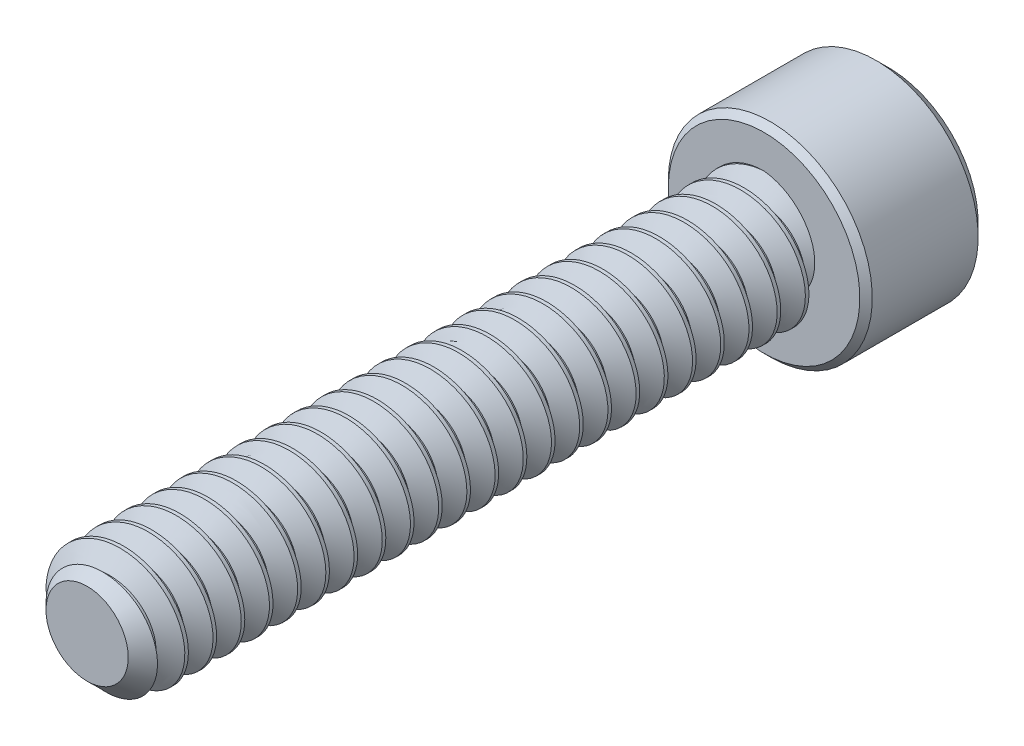
SolidWorks part; units mm, degrees
ref_plane "Front Plane" through (0, 0, 0) normal (0, 0, 1) x (1, 0, 0)
ref_plane "Top Plane" through (0, 0, 0) normal (0, 1, 0) x (1, 0, 0)
ref_plane "Right Plane" through (0, 0, 0) normal (1, 0, 0) x (0, 0, -1)
sketch "Sketch1" plane through (0, 0, 0) normal (0, 0, 1) x (1, 0, 0)
  line L0 (0, 1.7526) -> (0, -1.7526) construction
  circle A0 centre (0, 0) radius 1.7526
  dimension "OD" = 3.5052
extrude "Extrude1" add sketch "Sketch1" against normal blind 19.05
sketch "Sketch2" plane through (0, 0, 0) normal (0, 0, 1) x (1, 0, 0)
  circle A0 centre (0, 0) radius 1.7526 construction
  circle A1 centre (0, 0) radius 1.7526
curve "Helix/Spiral1" pitch 0.7937 height 19.8438 turns 25 parameters "pitch"=0.7937
chamfer "Chamfer3" distance 0.5953 angle 45 1 edges at (1.7526, 0, 0)
sketch "Sketch3" plane through (0, 0, 0) normal (1, 0, 0) x (0, 0, -1)
  line L0 (-0.6945, 1.7526) -> (-0.3969, 1.237)
  line L1 (-0.3969, 1.237) -> (-0.2977, 1.237)
  line L2 (-0.2977, 1.237) -> (0, 1.7526)
  line L3 (-0.6945, 1.7526) -> (0, 1.7526)
  line L4 (-0.3473, 1.7526) -> (-0.3473, 1.237) construction
  line L5 (-0.5457, 1.4948) -> (-0.1488, 1.4948) construction
  line L6 (0, 1.7526) -> (0, -1.7526) construction
  dimension "D1" = 0.0992
  dimension "D2" = 0.3969
  dimension "D3" = 60
sweep "Cut-Sweep1" cut profiles "Sketch3" path "Helix/Spiral1"
sketch "Sketch6" plane through (0, 0, -19.05) normal (0, 0, -1) x (-1, 0, 0)
  circle A0 centre (0, 0) radius 2.8702
  dimension "head dia" = 5.7404
extrude "Extrude2" add sketch "Sketch6" along normal blind 3.5052
sketch "Sketch7" plane through (0, 0, -22.5552) normal (0, 0, -1) x (-1, 0, 0)
  line L1 (0, 1.604) -> (-1.3891, 0.802)
  line L2 (-1.3891, 0.802) -> (-1.3891, -0.802)
  line L3 (-1.3891, -0.802) -> (0, -1.604)
  line L4 (0, -1.604) -> (1.3891, -0.802)
  line L5 (1.3891, -0.802) -> (1.3891, 0.802)
  line L6 (1.3891, 0.802) -> (0, 1.604)
  circle A0 centre (0, 0) radius 1.3891 construction
  dimension "hex dia" = 2.7781
extrude "Cut-Extrude1" cut sketch "Sketch7" against normal blind 2.0836
sketch "Sketch8" plane through (0, 0, -22.5552) normal (0, 0, -1) x (-1, 0, 0)
  circle A0 centre (0, 0) radius 1.604
extrude "Cut-Extrude2" cut sketch "Sketch8" against normal blind 0.3505 draft 45
chamfer "Chamfer1" distance 0.3505 angle 45 1 edges at (-2.8702, 0, -22.5552)
chamfer "Chamfer2" distance 0.1753 angle 45 1 edges at (-2.8702, 0, -19.05)
sketch "Sketch9" plane through (0, 0, 0) normal (1, 0, 0) x (0, 0, -1)
  line L0 (0, 1.7526) -> (0, -1.7526) construction
  line L1 (4.3656, 1.7526) -> (4.3656, -1.7526) construction
  line L2 (19.05, 2.8702) -> (19.05, -2.8702) construction
  line L3 (22.5552, 2.8702) -> (22.5552, -2.8702) construction
  line L4 (22.5552, 0) -> (0, 0) construction
  dimension "D1" = 4.3656
  dimension "D2" = 3.5052
  dimension "D3" = 5.7404
  dimension "D4" = 19.05
equation "\"D3@Helix/Spiral1\" = \"screw length@Extrude1\"+\"pitch@Helix/Spiral1\""
equation "\"D1@Sketch3\" = \"pitch@Helix/Spiral1\"*.125"
equation "\"D2@Sketch3\" = \"pitch@Helix/Spiral1\"*.5"
equation "\"D1@Cut-Extrude1\" = \"hex dia@Sketch7\"*.75"
equation "\"D1@Chamfer1\" = \"head depth@Extrude2\"/10"
equation "\"D1@Sketch9\" = \"pitch@Helix/Spiral1\"*5.5"
equation "\"D1@Chamfer2\" = \"D1@Chamfer1\"/2"
equation "\"D1@Cut-Extrude2\" = \"D1@Chamfer2\"*2"
equation "\"D1@Chamfer3\" = \"pitch@Helix/Spiral1\"*.750"
equation "\"D2@Sketch9\" = \"head depth@Extrude2\""
equation "\"D3@Sketch9\" = \"head dia@Sketch6\""
equation "\"D4@Sketch9\" = \"screw length@Extrude1\""
